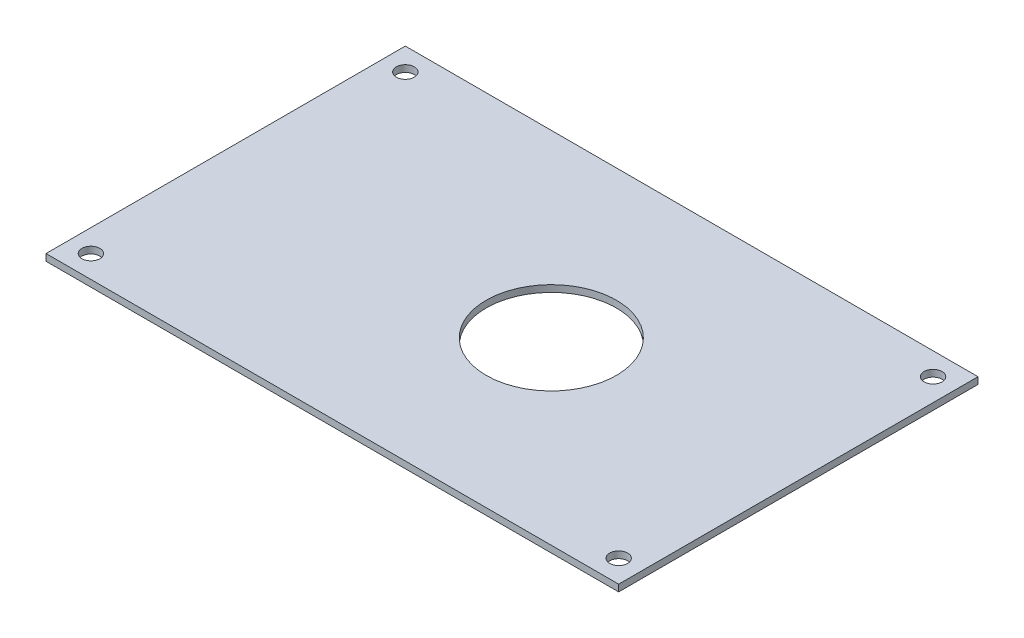
SolidWorks part; units mm, degrees
ref_plane "Front Plane" through (0, 0, 0) normal (0, 0, 1) x (1, 0, 0)
ref_plane "Top Plane" through (0, 0, 0) normal (0, 1, 0) x (1, 0, 0)
ref_plane "Right Plane" through (0, 0, 0) normal (1, 0, 0) x (0, 0, -1)
sketch "Sketch1" plane through (0, 0, 0) normal (0, 1, 0) x (1, 0, 0)
  line L1 (-127.5, -80) -> (127.5, -80)
  line L2 (-127.5, -80) -> (-127.5, 80)
  line L3 (-127.5, 80) -> (127.5, 80)
  line L4 (127.5, -80) -> (127.5, 80)
  line L5 (-127.5, -80) -> (127.5, 80) construction
  line L6 (-127.5, 80) -> (127.5, -80) construction
  point P0 (0, 0)
  dimension "D1" = 255
  dimension "D2" = 160
extrude "Boss-Extrude1" add sketch "Sketch1" along normal blind 3
sketch "Sketch2" plane through (0, 3, 0) normal (0, 1, 0) x (1, 0, 0)
  line L0 (-127.5, -80) -> (127.5, -80) construction
  line L1 (-127.5, 80) -> (-127.5, -80) construction
  line L2 (-127.5, 0) -> (127.5, 0) construction
  line L3 (127.5, -80) -> (127.5, 80) construction
  line L4 (0, -80) -> (0, 80) construction
  line L5 (127.5, 80) -> (-127.5, 80) construction
  circle A0 centre (-117.5, -70) radius 4
  circle A1 centre (-117.5, 70) radius 4
  circle A2 centre (117.5, -70) radius 4
  circle A3 centre (117.5, 70) radius 4
  point P12 (0, 0)
  point P18 (0, 0)
  dimension "D1" = 8
  dimension "D2" = 10
  dimension "D3" = 10
extrude "Cut-Extrude1" cut sketch "Sketch2" against normal blind 3
sketch "Sketch3" plane through (0, 3, 0) normal (0, 1, 0) x (1, 0, 0)
  line L0 (-127.5, 80) -> (-127.5, -80) construction
  circle A0 centre (17.5, 0) radius 29
  dimension "D1" = 58
  dimension "D2" = 145
extrude "Cut-Extrude2" cut sketch "Sketch3" against normal blind 3
